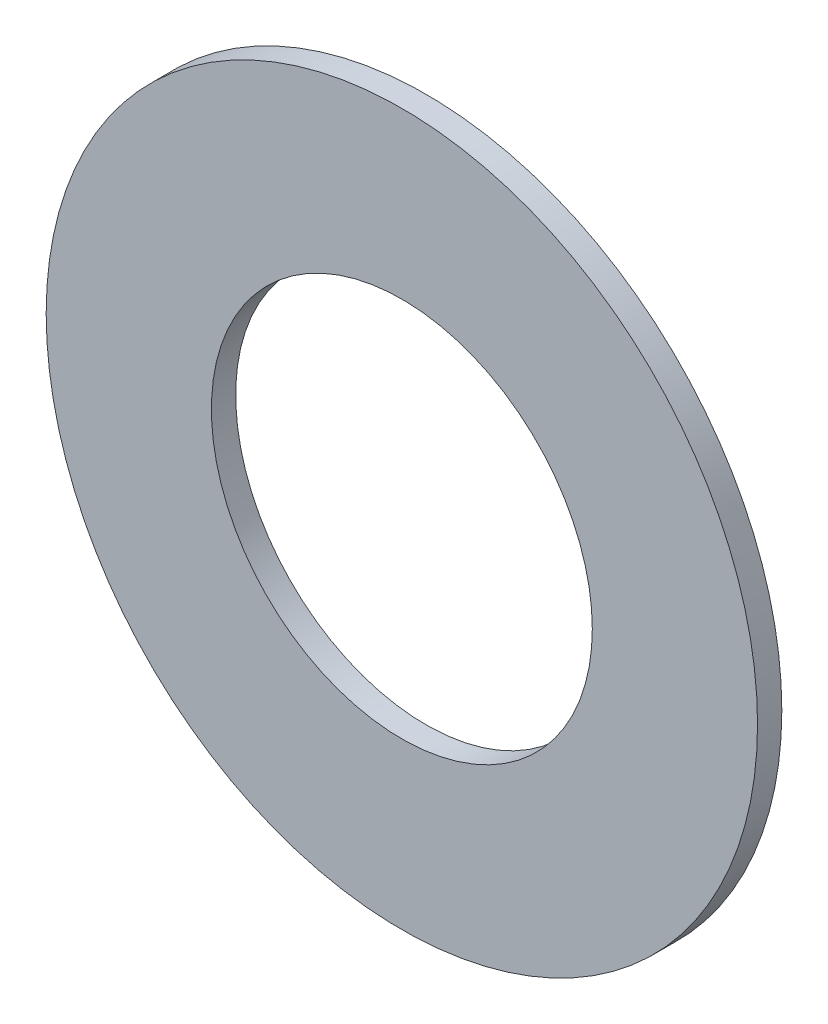
SolidWorks part; units mm, degrees
material "Alloy Steel"
ref_plane "Front Plane" through (0, 0, 0) normal (0, 0, 1) x (1, 0, 0)
ref_plane "Top Plane" through (0, 0, 0) normal (0, 1, 0) x (1, 0, 0)
ref_plane "Right Plane" through (0, 0, 0) normal (1, 0, 0) x (0, 0, -1)
sketch "Sketch1" plane through (0, 0, 0) normal (0, 0, 1) x (1, 0, 0)
  line L0 (-6.35, 0) -> (6.35, 0) construction
  circle A0 centre (0, 0) radius 11.9062 construction
  circle A1 centre (0, 0) radius 6.3754 construction
  dimension "OD" = 23.8125
  dimension "ID" = 12.7508
  dimension "For Shaft Diameter" = 12.7
sketch "Sketch2" plane through (0, 0, 0) normal (1, 0, 0) x (0, 0, -1)
  line L4 (0.4064, 11.9062) -> (-0.4064, 11.9062) construction
  point P0 (0, 11.9062)
  dimension "Thickness" = 0.8128
sketch "Sketch3" plane through (0, 0, 0) normal (0, 0, 1) x (1, 0, 0)
  circle A0 centre (0, 0) radius 6.3754 construction
  circle A1 centre (0, 0) radius 11.9062 construction
  circle A3 centre (0, 0) radius 6.3754
  circle A5 centre (0, 0) radius 11.9062
extrude "Boss-Extrude1" add sketch "Sketch3" against normal up to vertex (-0.4064 mm away) and the other way up to vertex (-0.4064 mm away) up to point (0, 11.9062, 0.4064) other way up to point (0, 11.9062, -0.4064)
equation "\"D1\"= \"Thickness@Sketch2\""
